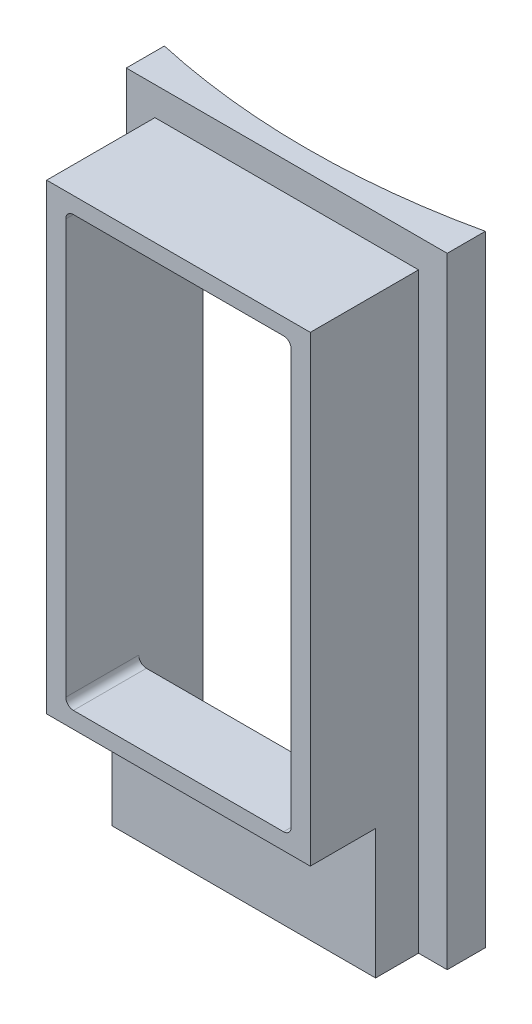
SolidWorks part; units mm, degrees
ref_plane "Front Plane" through (0, 0, 0) normal (0, 0, 1) x (1, 0, 0)
ref_plane "Top Plane" through (0, 0, 0) normal (0, 1, 0) x (1, 0, 0)
ref_plane "Right Plane" through (0, 0, 0) normal (1, 0, 0) x (0, 0, -1)
sketch "Sketch1" plane through (0, 0, 0) normal (0, 0, 1) x (1, 0, 0)
  line L1 (-46.99, 86.36) -> (59.69, 86.36)
  line L2 (-46.99, 86.36) -> (-46.99, -119.888)
  line L3 (-46.99, -119.888) -> (59.69, -119.888)
  line L4 (59.69, 86.36) -> (59.69, -119.888)
  dimension "D1" = 106.68
  dimension "D2" = 206.248
extrude "Extrude1" add sketch "Sketch1" along normal blind 252.4252
sketch "Sketch2" plane through (0, 86.36, 0) normal (0, 1, 0) x (-1, 0, 0)
  line L0 (-59.69, 0) -> (46.99, 0) construction
  circle A1 centre (-6.35, 0) radius 245.618
sketch "Sketch7" plane through (0, 0, 252.4252) normal (0, 0, 1) x (1, 0, 0)
  line L0 (-46.99, 86.36) -> (-46.99, -119.888) construction
  line L1 (-37.465, 76.835) -> (50.165, 76.835)
  line L2 (-37.465, 76.835) -> (-37.465, -119.888)
  line L3 (-37.465, -119.888) -> (50.165, -119.888)
  line L4 (50.165, 76.835) -> (50.165, -119.888)
  line L5 (59.69, -119.888) -> (59.69, 86.36) construction
  line L6 (59.69, 86.36) -> (-46.99, 86.36) construction
  line L7 (-46.99, -119.888) -> (59.69, -119.888) construction
  point P8 (6.35, 76.835)
  point P9 (0, 0)
  dimension "D1" = 9.525
  dimension "D2" = 9.525
  dimension "D3" = 9.525
extrude "Extrude5" add sketch "Sketch7" along normal blind 35.9842
sketch "Sketch4" plane through (0, 0, 252.4252) normal (0, 0, 1) x (1, 0, 0)
  line L0 (59.69, 86.36) -> (-46.99, 86.36) construction
  line L1 (-31.115, 71.374) -> (43.815, 71.374)
  line L2 (-31.115, 71.374) -> (-31.115, -71.374)
  line L3 (-31.115, -71.374) -> (43.815, -71.374)
  line L4 (43.815, 71.374) -> (43.815, -71.374)
  line L5 (50.165, 76.835) -> (-37.465, 76.835) construction
  line L6 (50.165, 76.835) -> (-37.465, 76.835) construction
  point P4 (6.35, 71.374)
  point P5 (6.35, 86.36)
  point P6 (6.35, 76.835)
  dimension "D1" = 5.461
  dimension "D2" = 142.748
extrude "Extrude2" cut sketch "Sketch4" against normal blind 273.8502 and the other way blind 42.08
sketch "Sketch10" plane through (0, 0, 0) normal (0, 0, -1) x (-1, 0, 0)
  line L0 (46.99, -119.888) -> (-59.69, -119.888) construction
  line L1 (-43.815, 71.374) -> (31.115, 71.374)
  line L2 (-43.815, 71.374) -> (-43.815, 74.295)
  line L3 (-43.815, 74.295) -> (31.115, 74.295)
  line L4 (31.115, 71.374) -> (31.115, 74.295)
  line L5 (-43.815, -71.374) -> (31.115, -71.374)
  line L6 (-43.815, -71.374) -> (-43.815, -117.348)
  line L7 (-43.815, -117.348) -> (31.115, -117.348)
  line L8 (31.115, -71.374) -> (31.115, -117.348)
  dimension "D1" = 2.54
extrude "Extrude8" cut sketch "Sketch10" against normal blind 264.16
sketch "Sketch11" plane through (0, 0, 264.16) normal (0, 0, -1) x (-1, 0, 0)
  line L0 (-43.815, 71.374) -> (31.115, 71.374) construction
  line L1 (31.115, 74.295) -> (-43.815, 74.295)
  line L2 (31.115, 74.295) -> (31.115, 71.374)
  line L3 (31.115, 71.374) -> (-43.815, 71.374)
  line L4 (-43.815, 74.295) -> (-43.815, 71.374)
extrude "Extrude9" cut sketch "Sketch11" against normal blind 21.59
fillet "Fillet1" radius 2.54 8 edges at (43.815, -71.374, 276.2847) (-31.115, -71.374, 276.2847) (43.815, 71.374, 287.0797) (-31.115, 71.374, 287.0797) (43.815, -117.348, 132.08) (-31.115, -117.348, 132.08) (-31.115, 74.295, 142.875) (43.815, 74.295, 142.875)
extrude "Extrude4" cut sketch "Sketch2" against normal blind 230
sketch "Sketch12" plane through (0, 0, 288.4094) normal (0, 0, 1) x (1, 0, 0)
  line L0 (50.165, -119.888) -> (50.165, 76.835) construction
  line L1 (-37.465, -119.888) -> (50.165, -119.888)
  line L2 (-37.465, -119.888) -> (-37.465, -76.835)
  line L3 (-37.465, -76.835) -> (50.165, -76.835)
  line L4 (50.165, -119.888) -> (50.165, -76.835)
  dimension "D1" = 5.461
extrude "Extrude10" cut sketch "Sketch12" against normal blind 21.7094
